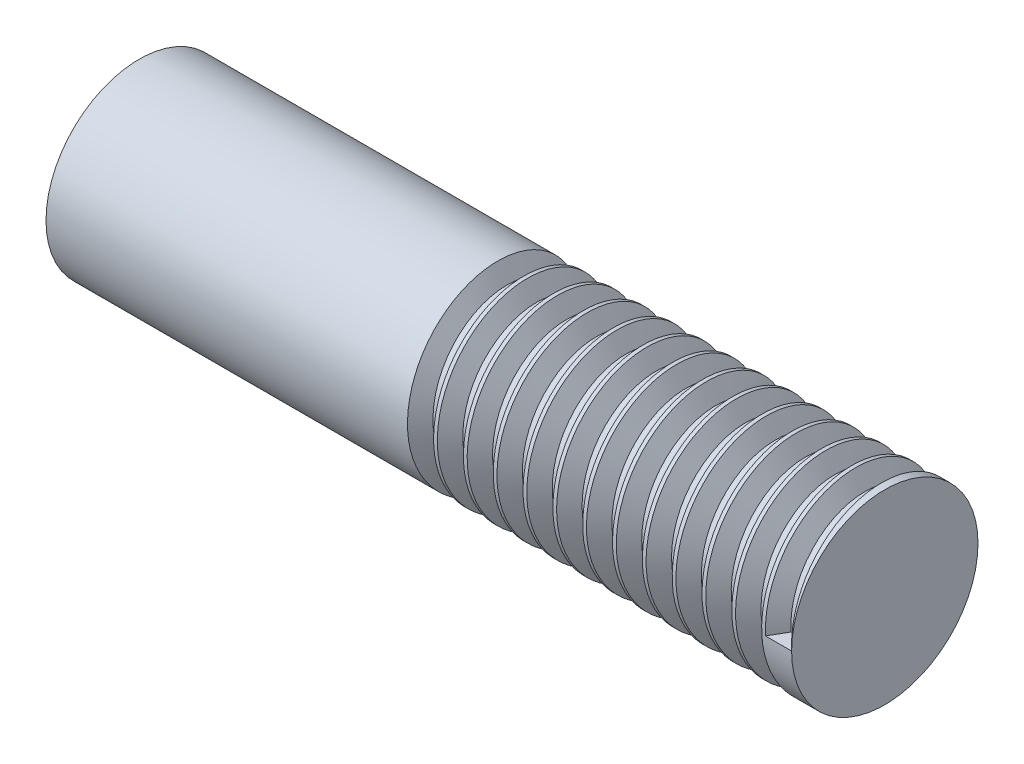
SolidWorks part; units mm, degrees
ref_plane "Front Plane" through (0, 0, 0) normal (0, 0, 1) x (1, 0, 0)
ref_plane "Top Plane" through (0, 0, 0) normal (0, 1, 0) x (1, 0, 0)
ref_plane "Right Plane" through (0, 0, 0) normal (1, 0, 0) x (0, 0, -1)
sketch "Sketch1" plane through (0, 0, 0) normal (1, 0, 0) x (0, 0, -1)
  circle A0 centre (0, 0) radius 2.5
extrude "Boss-Extrude1" add sketch "Sketch1" along normal blind 20
thread "Thread1" pitch 0.8 method cut profile "Thread Profile1" start angle 0, offset 0, length 10, pitch 0.8, diameter 5
ref_plane "Plane1" through (20, 0, 2.5) normal (0, -1, 0) x (0, 0, 1)
sketch "Thread Profile1" plane through (20, 0, 2.5) normal (0, -1, 0) x (0, 0, 1)
  line L0 (0, 0) -> (0, 0.8) construction
  line L11 (0, 0) -> (0, 0.7)
  line L12 (0, 0.7) -> (-0.433, 0.45)
  line L13 (-0.433, 0.45) -> (-0.433, 0.25)
  line L15 (-0.433, 0.25) -> (0, 0)
  line L17 (-0.433, 0.35) -> (0, 0.35) construction
  point P2 (0, 0)
  dimension "Pitch" = 0.8
  dimension "Profile_Angle" = 60
  dimension "Profile_Land" = 0.2
  dimension "Profile_Height" = 0.433
